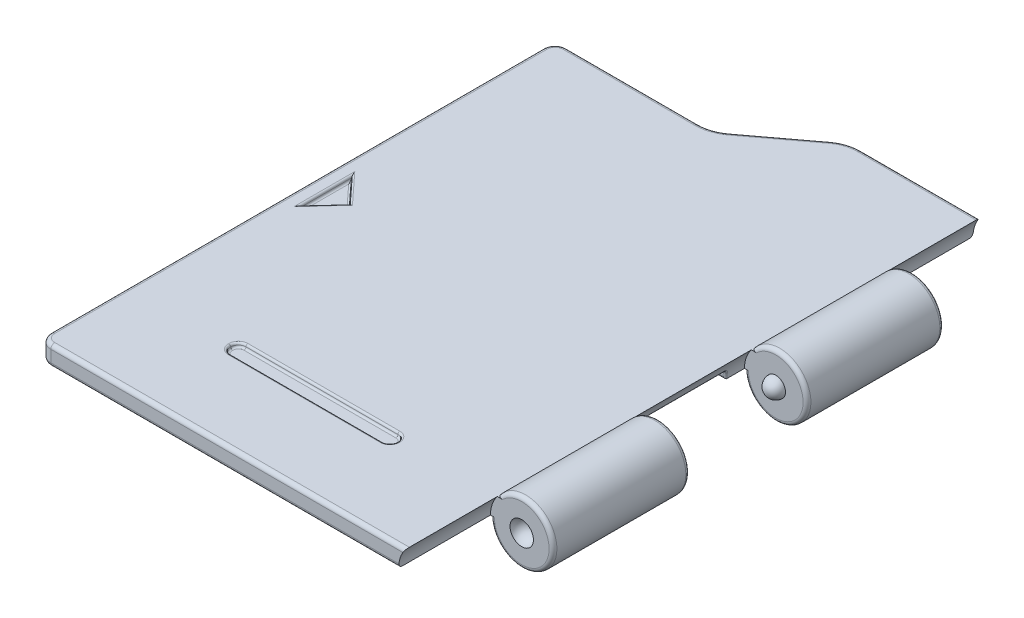
SolidWorks part; units mm, degrees
ref_plane "정면" through (0, 0, 0) normal (0, 0, 1) x (1, 0, 0)
ref_plane "윗면" through (0, 0, 0) normal (0, 1, 0) x (1, 0, 0)
ref_plane "우측면" through (0, 0, 0) normal (1, 0, 0) x (0, 0, -1)
sketch "스케치1" plane through (0, 0, 0) normal (0, 0, 1) x (1, 0, 0)
  line L1 (-8, 0) -> (-100, 0)
  line L3 (-6.245, 5) -> (-100, 5)
  line L4 (-100, 0) -> (-100, 5)
  arc A0 (-8, 0) -> (-6.245, 5) centre (0, 0) ccw
  dimension "D1" = 16
extrude "보스-돌출1" add sketch "스케치1" along normal blind 147
sketch "스케치2" plane through (0, 0, 147) normal (0, 0, 1) x (1, 0, 0)
  circle A0 centre (0, 0) radius 8
extrude "컷-돌출1" cut sketch "스케치2" against normal blind 23.5
sketch "스케치3" plane through (0, 0, 0) normal (0, 0, -1) x (-1, 0, 0)
  circle A0 centre (0, 0) radius 8
extrude "컷-돌출2" cut sketch "스케치3" against normal blind 23.5
sketch "스케치4" plane through (0, 5, 0) normal (0, 1, 0) x (1, 0, 0)
  line L1 (-100, 0) -> (-40, 0)
  line L2 (-100, 0) -> (-100, -15)
  line L3 (-100, -15) -> (-60, -15)
  line L5 (-60, -15) -> (-40, 0)
  dimension "D1" = 40
  dimension "D2" = 20
  dimension "D3" = 15
extrude "컷-돌출3" cut sketch "스케치4" against normal blind 5
fillet "필렛1" radius 10 2 edges at (-40, 2.5, 0) (-60, 2.5, 15)
fillet "필렛2" radius 3 2 edges at (-100, 2.5, 147) (-100, 2.5, 15)
fillet "필렛3" radius 1 18 edges at (-51.6225, 5, 147) (-99.1213, 5, 146.1213) (-21.4558, 5, 0) (-39.8289, 5, 0.5132) (-50, 5, 7.5) (-60.1711, 5, 14.4868) (-80.1667, 5, 15) (-99.1213, 5, 15.8787) (-52.5, 0, 147) (-99.1213, 0, 146.1213) (-22.3333, 0, 0) (-39.8289, 0, 0.5132) (-50, 0, 7.5) (-60.1711, 0, 14.4868) (-80.1667, 0, 15) (-99.1213, 0, 15.8787) (-100, 5, 81) (-100, 0, 81)
fillet "필렛4" radius 1 2 edges at (7.5485, -2.6495, 23.5) (7.5485, -2.6495, 123.5)
sketch "스케치5" plane through (0, 5, 0) normal (0, 1, 0) x (1, 0, 0)
  line L0 (-99, -18) -> (-99, -144) construction
  line L1 (-72.05, -122) -> (-33.195, -122)
  line L2 (-74, -123.95) -> (-74, -124.05)
  line L3 (-72.05, -126) -> (-33.195, -126)
  line L4 (-31.245, -123.95) -> (-31.245, -124.05)
  line L5 (-6.245, -146) -> (-6.245, -123.5) construction
  line L6 (-97, -146) -> (-6.245, -146) construction
  line L7 (-96, -71) -> (-96, -84)
  line L8 (-96, -84) -> (-90, -77.5)
  line L9 (-90, -77.5) -> (-96, -71)
  line L10 (-63.3333, -16) -> (-97, -16) construction
  arc A0 (-33.195, -126) -> (-31.245, -124.05) centre (-33.195, -124.05) ccw
  arc A1 (-33.195, -122) -> (-31.245, -123.95) centre (-33.195, -123.95) cw
  arc A2 (-74, -124.05) -> (-72.05, -126) centre (-72.05, -124.05) ccw
  arc A3 (-72.05, -122) -> (-74, -123.95) centre (-72.05, -123.95) ccw
  point P12 (-31.245, -126)
  point P15 (-31.245, -122)
  dimension "D5" = 1.95
  dimension "D1" = 25
  dimension "D2" = 25
  dimension "D3" = 4
  dimension "D4" = 20
  dimension "D6" = 3
  dimension "D7" = 6
  dimension "D8" = 55
  dimension "D9" = 13
extrude "컷-돌출4" cut sketch "스케치5" against normal blind 1
fillet "필렛5" radius 0.5 22 edges at (-31.8161, 5, 122.5711) (-31.245, 5, 124) (-31.8161, 5, 125.4289) (-52.6225, 5, 126) (-73.4289, 5, 125.4289) (-74, 5, 124) (-73.4289, 5, 122.5711) (-52.6225, 4, 126) (-73.4289, 4, 125.4289) (-74, 4, 124) (-73.4289, 4, 122.5711) (-52.6225, 4, 122) (-31.8161, 4, 122.5711) (-31.245, 4, 124) (-31.8161, 4, 125.4289) (-93, 4, 80.75) (-96, 4, 77.5) (-93, 4, 74.25) (-52.6225, 5, 122) (-93, 5, 80.75) (-93, 5, 74.25) (-96, 5, 77.5)
ref_plane "평면1" through (0, 0, 73.5) normal (0, 0, 1) x (1, 0, 0)
sketch "스케치6" plane through (0, 0, 73.5) normal (0, 0, 1) x (1, 0, 0)
  circle A0 centre (0, 0) radius 8
extrude "컷-돌출5" cut sketch "스케치6" against normal mid plane 30
fillet "필렛6" radius 1 2 edges at (7.5485, -2.6495, 58.5) (7.5485, -2.6495, 88.5)
sketch "스케치7" plane through (0, 0, 123.5) normal (0, 0, 1) x (1, 0, 0)
  line L0 (0, 3) -> (0, -3.6179) construction
  line L1 (0, 3) -> (0, -3)
  arc A0 (0, 3) -> (0, -3) centre (0, 0) ccw
  dimension "D1" = 6
revolve "컷-회전1" cut sketch "스케치7" angle 360 about L0
sketch "스케치8" plane through (0, 0, 23.5) normal (0, 0, -1) x (-1, 0, 0)
  line L0 (0, 3) -> (0, -3) construction
  line L1 (0, 3) -> (0, -3)
  arc A0 (0, 3) -> (0, -3) centre (0, 0) ccw
  dimension "D1" = 6
revolve "컷-회전2" cut sketch "스케치8" angle 360 about L0
sketch "스케치9" plane through (0, 0, 88.5) normal (0, 0, -1) x (-1, 0, 0)
  line L0 (0, 2.5) -> (0, -2.5) construction
  line L1 (0, 2.5) -> (0, -2.5)
  arc A0 (0, 2.5) -> (0, -2.5) centre (0, 0) ccw
  dimension "D1" = 5
revolve "회전2" add sketch "스케치9" angle 360 about L0
sketch "스케치10" plane through (0, 0, 58.5) normal (0, 0, 1) x (1, 0, 0)
  line L0 (0, 2.5) -> (0, -2.5) construction
  line L1 (0, 2.5) -> (0, -2.5)
  arc A0 (0, 2.5) -> (0, -2.5) centre (0, 0) ccw
  dimension "D1" = 2.5
revolve "회전3" add sketch "스케치10" angle 360 about L0
sketch "스케치11" plane through (0, 0, 0) normal (0, -1, 0) x (-1, 0, 0)
  line L1 (8, -58.5) -> (8, -88.5) construction
  line L3 (30, -93.5) -> (30, -133.5)
  line L4 (60, -18.5) -> (40, -18.5)
  line L5 (70, -28.5) -> (70, -133.5)
  line L6 (60, -143.5) -> (40, -143.5)
  line L7 (30, -28.5) -> (30, -53.5)
  line L8 (20, -83.5) -> (8, -83.5)
  line L9 (8, -83.5) -> (0.7049, -83.5)
  line L10 (20, -63.5) -> (8, -63.5)
  line L12 (8, -63.5) -> (0.7049, -63.5)
  line L13 (0.7049, -83.5) -> (0.7049, -63.5)
  arc A0 (40, -18.5) -> (30, -28.5) centre (40, -28.5) ccw
  arc A1 (60, -18.5) -> (70, -28.5) centre (60, -28.5) cw
  arc A2 (40, -143.5) -> (30, -133.5) centre (40, -133.5) cw
  arc A3 (70, -133.5) -> (60, -143.5) centre (60, -133.5) cw
  arc A4 (30, -53.5) -> (20, -63.5) centre (20, -53.5) cw
  arc A5 (20, -83.5) -> (30, -93.5) centre (20, -93.5) cw
  point P16 (30, -143.5)
  point P19 (70, -143.5)
  point P24 (30, -83.5)
  dimension "D5" = 10
  dimension "D1" = 10
  dimension "D2" = 40
  dimension "D3" = 20
  dimension "D4" = 45
  dimension "D6" = 60
extrude "컷-돌출7" cut sketch "스케치11" against normal blind 2
fillet "필렛7" radius 0.5 29 edges at (-7.9362, 1.008, 83.5) (-7.9362, 1.008, 63.5) (-14, 0, 83.5) (-14, 0, 63.5) (-27.0711, 0, 60.5711) (-30, 0, 41) (-32.9289, 0, 21.4289) (-50, 0, 18.5) (-67.0711, 0, 21.4289) (-70, 0, 81) (-67.0711, 0, 140.5711) (-50, 0, 143.5) (-32.9289, 0, 140.5711) (-30, 0, 113.5) (-7.746, 2, 73.5) (-13.873, 2, 63.5) (-27.0711, 2, 60.5711) (-30, 2, 41) (-32.9289, 2, 21.4289) (-50, 2, 18.5) (-67.0711, 2, 21.4289) (-70, 2, 81) (-67.0711, 2, 140.5711) (-50, 2, 143.5) (-32.9289, 2, 140.5711) (-30, 2, 113.5) (-27.0711, 2, 86.4289) (-13.873, 2, 83.5) (-27.0711, 0, 86.4289)
